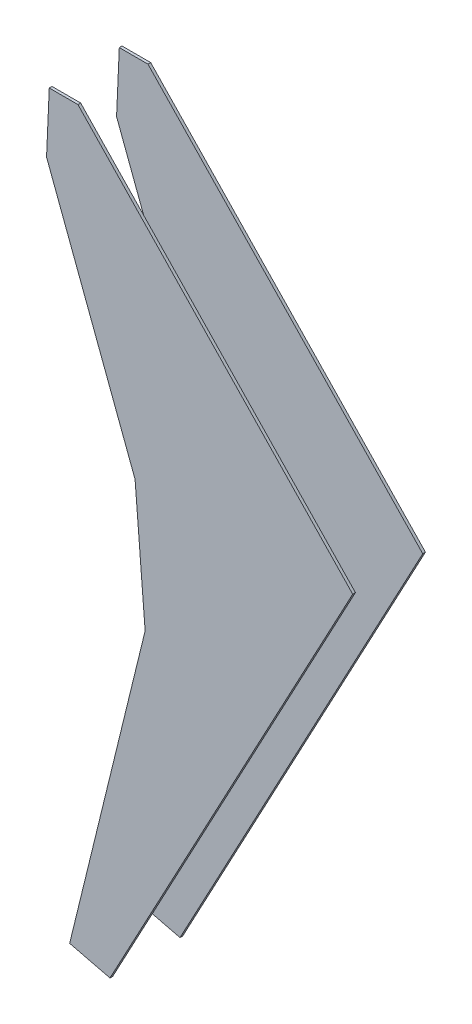
SolidWorks part; units mm, degrees
ref_plane "Front Plane" through (0, 0, 0) normal (0, 0, 1) x (1, 0, 0)
ref_plane "Top Plane" through (0, 0, 0) normal (0, 1, 0) x (1, 0, 0)
ref_plane "Right Plane" through (0, 0, 0) normal (1, 0, 0) x (0, 0, -1)
sketch "Sketch1" plane through (0, 0, 0) normal (0, 0, 1) x (1, 0, 0)
  line L0 (295.6751, 161.4802) -> (-235.0917, 715.0626)
  line L1 (-251.0267, -696.0134) -> (-173.2027, -715.0626)
  line L2 (-295.6751, 596.9214) -> (-124.7233, 143.4473)
  line L3 (-124.7233, 143.4473) -> (-105.2282, -100.3641)
  line L4 (-251.0267, -696.0134) -> (-105.2282, -100.3641)
  line L5 (-173.2027, -715.0626) -> (295.6751, 161.4802)
  line L6 (-290.4136, 715.0626) -> (-235.0917, 715.0626)
  line L7 (-295.6751, 596.9214) -> (-290.4136, 715.0626)
extrude "Boss-Extrude1" add sketch "Sketch1" along normal blind 5.25 from offset 65
extrude "Boss-Extrude2" add sketch "Sketch1<2>" against normal blind 5.25 from offset 65 offset against normal yes
sketch "Sketch1<2>" plane through (0, 0, 0) normal (0, 0, 1) x (1, 0, 0) same geometry as "Sketch1"
